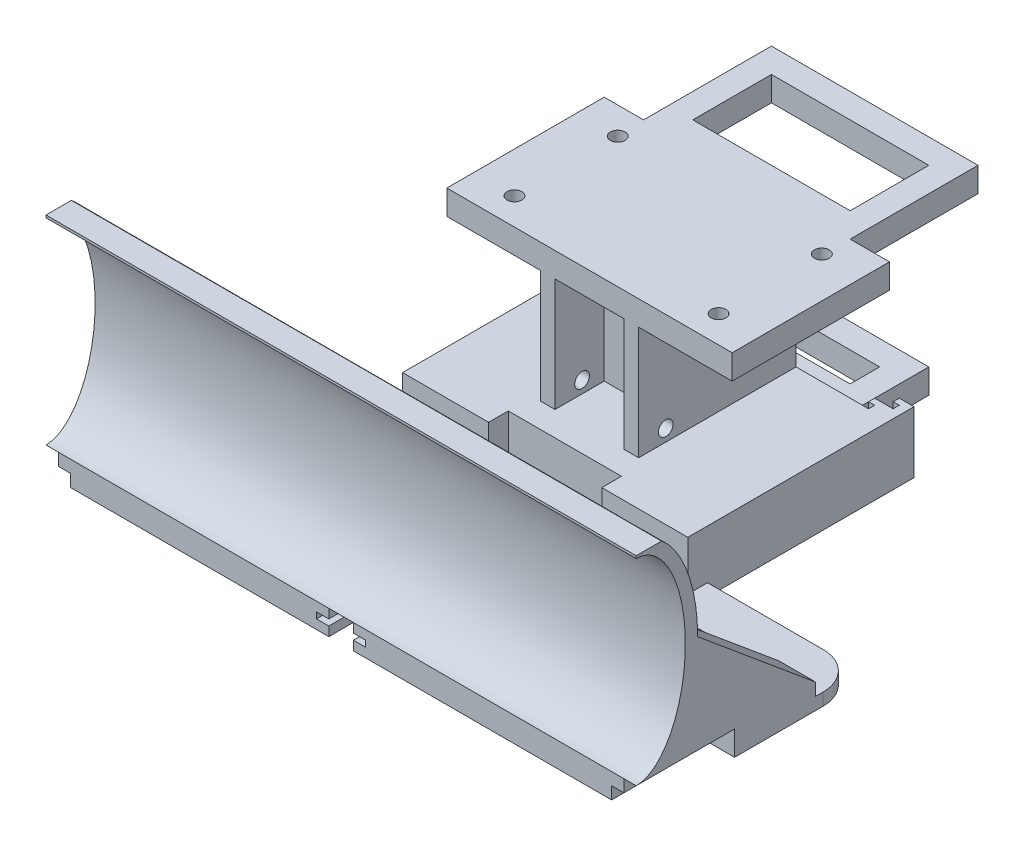
SolidWorks part; units mm, degrees
ref_plane "Alzado" through (0, 0, 0) normal (0, 0, 1) x (1, 0, 0)
ref_plane "Planta" through (0, 0, 0) normal (0, 1, 0) x (1, 0, 0)
ref_plane "Vista lateral" through (0, 0, 0) normal (1, 0, 0) x (0, 0, -1)
sketch "Base-Croquis" plane through (0, 0, 0) normal (0, 1, 0) x (1, 0, 0)
  line L1 (60, -60) -> (-60, -60)
  line L2 (60, -60) -> (60, 60)
  line L3 (60, 60) -> (-60, 60)
  line L4 (-60, -60) -> (-60, 60)
  line L5 (60, -60) -> (-60, 60) construction
  line L6 (60, 60) -> (-60, -60) construction
  point P0 (0, 0)
  dimension "D1" = 120
  dimension "D2" = 120
extrude "Base-Saliente" add sketch "Base-Croquis" along normal blind 5
sketch "Encaje-Ruedas-Croquis" plane through (0, 5, 0) normal (0, 1, 0) x (1, 0, 0)
  line L6 (60, 60) -> (29, 60)
  line L7 (60, 60) -> (60, 3)
  line L8 (60, 3) -> (29, 3)
  line L9 (29, 60) -> (29, 3)
  line L10 (0, -55) -> (0, 55) construction
  line L11 (-60, 3) -> (-29, 3)
  line L12 (-29, 60) -> (-29, 3)
  line L13 (-60, 60) -> (-29, 60)
  line L14 (-60, 60) -> (-60, 3)
  line L15 (60, 60) -> (60, 65) construction
  line L16 (60, 65) -> (-60, 65) construction
  line L17 (-60, 65) -> (-60, 60) construction
  line L18 (-31, 65) -> (-31, 60) construction
  line L19 (31, 65) -> (31, 60) construction
  dimension "D1" = 31
  dimension "D2" = 57
  dimension "D3" = 5
  dimension "D4" = 29
  dimension "D5" = 29
extrude "Encaje-Ruedas-Cortar" cut sketch "Encaje-Ruedas-Croquis" against normal blind 5
sketch "Caja-Placas-Croquis-1" plane through (0, 5, 0) normal (0, 1, 0) x (1, 0, 0)
  line L0 (29, 40) -> (-29, 40) construction
  line L1 (29, 60) -> (29, 3) construction
  line L2 (-29, 3) -> (-29, 60) construction
  line L3 (29, 60) -> (-29, 60) construction
  line L4 (-29, 8) -> (29, 8) construction
  line L5 (0, 8) -> (0, 40) construction
  line L7 (21, 8) -> (-21, 8)
  line L8 (21, 8) -> (21, 40)
  line L9 (21, 40) -> (-21, 40)
  line L10 (-21, 8) -> (-21, 40)
  line L11 (21, 8) -> (-21, 40) construction
  line L12 (21, 40) -> (-21, 8) construction
  line L13 (-29, 45) -> (29, 45)
  line L14 (-29, 45) -> (-29, 3)
  line L15 (-29, 3) -> (29, 3)
  line L16 (29, 45) -> (29, 3)
  point P12 (0, 24)
  dimension "D1" = 20
  dimension "D2" = 32
  dimension "D3" = 42
  dimension "D4" = 42
  dimension "D5" = 5
extrude "Caja-Placas-Saliente-1" add sketch "Caja-Placas-Croquis-1" along normal blind 5
sketch "Caja-Placas-Croquis-2" plane through (0, 5, 0) normal (0, 1, 0) x (1, 0, 0)
  line L0 (0, 3) -> (0, 45) construction
  line L1 (-29, 3) -> (29, 3) construction
  line L2 (29, 45) -> (-29, 45) construction
  line L4 (21, 8) -> (-21, 8)
  line L5 (21, 8) -> (21, 40)
  line L6 (21, 40) -> (-21, 40)
  line L7 (-21, 8) -> (-21, 40)
  line L8 (21, 8) -> (-21, 40) construction
  line L9 (21, 40) -> (-21, 8) construction
  point P6 (0, 24)
extrude "Caja-Placas-Cortar-2" cut sketch "Caja-Placas-Croquis-2" against normal blind 2.5
sketch "Caja-Placas-Croquis-3" plane through (0, 10, 0) normal (0, 1, 0) x (1, 0, 0)
  line L1 (-29, 45) -> (29, 45)
  line L2 (-29, 45) -> (-29, 3)
  line L3 (-29, 3) -> (29, 3)
  line L4 (29, 45) -> (29, 3)
extrude "Caja-Placas-Saliente-3" add sketch "Caja-Placas-Croquis-3" along normal blind 2.5
sketch "Caja-Placas-Croquis-4" plane through (0, 12.5, 0) normal (0, 1, 0) x (1, 0, 0)
  line L0 (-29, 40) -> (-29, 42.5) construction
  line L1 (-29, 42.5) -> (29, 42.5) construction
  line L2 (29, 45) -> (29, 3) construction
  line L3 (-29, 42.5) -> (-29, 45) construction
  line L4 (-29, 45) -> (29, 45) construction
  line L5 (29, 40) -> (-29, 40) construction
  line L6 (-29, 43.75) -> (29, 43.75) construction
  line L7 (-29, 41.25) -> (29, 41.25) construction
  line L8 (23.5, 42.5) -> (26, 42.5)
  line L9 (-23.5, 40) -> (23.5, 40)
  line L10 (-23.5, 41.25) -> (-23.5, 42.5)
  line L12 (23.5, 41.25) -> (23.5, 42.5)
  line L13 (-26, 45) -> (26, 45)
  line L14 (-26, 45) -> (-26, 43.75)
  line L15 (-26, 42.5) -> (-23.5, 42.5)
  line L16 (26, 45) -> (26, 43.75)
  line L17 (26, 43.75) -> (27.25, 43.75)
  line L19 (26, 42.5) -> (27.25, 42.5)
  line L20 (27.25, 43.75) -> (27.25, 42.5)
  line L21 (23.5, 41.25) -> (24.75, 41.25)
  line L23 (23.5, 40) -> (24.75, 40)
  line L24 (24.75, 41.25) -> (24.75, 40)
  line L25 (-23.5, 40) -> (-24.75, 40)
  line L27 (-23.5, 41.25) -> (-24.75, 41.25)
  line L28 (-24.75, 40) -> (-24.75, 41.25)
  line L29 (-26, 42.5) -> (-27.25, 42.5)
  line L31 (-26, 43.75) -> (-27.25, 43.75)
  line L32 (-27.25, 42.5) -> (-27.25, 43.75)
  dimension "D1" = 47
  dimension "D2" = 5.5
  dimension "D3" = 52
  dimension "D4" = 3
  dimension "D5" = 1.25
  dimension "D6" = 1.25
  dimension "D7" = 1.25
  dimension "D8" = 1.25
extrude "Caja-Placas-Cortar-4" cut sketch "Caja-Placas-Croquis-4" against normal blind 7.5
sketch "Caja-Placas-Croquis-5" plane through (0, 0, 0) normal (0, -1, 0) x (-1, 0, 0)
  line L0 (0, 8) -> (0, 40) construction
  line L1 (15.5, 34.5) -> (-15.5, 34.5)
  line L2 (15.5, 34.5) -> (15.5, 13.5)
  line L3 (15.5, 13.5) -> (-15.5, 13.5)
  line L4 (-15.5, 34.5) -> (-15.5, 13.5)
  line L5 (15.5, 34.5) -> (-15.5, 13.5) construction
  line L6 (15.5, 13.5) -> (-15.5, 34.5) construction
  point P0 (0, 24)
  dimension "D1" = 21
  dimension "D2" = 31
extrude "Caja-Placas-Cortar-5" cut sketch "Caja-Placas-Croquis-5" against normal blind 2.5
sketch "Caja-Motores-Croquis-1" plane through (0, 12.5, 0) normal (0, 1, 0) x (1, 0, 0)
  line L0 (21, 8) -> (-21, 40) construction
  line L1 (-10, 8) -> (10, 8)
  line L2 (-10, 8) -> (-10, 40)
  line L3 (-10, 40) -> (10, 40)
  line L4 (10, 8) -> (10, 40)
  line L5 (-10, 8) -> (10, 40) construction
  line L6 (-10, 40) -> (10, 8) construction
  line L7 (21, 40) -> (-21, 40) construction
  point P0 (0, 24)
  dimension "D1" = 20
extrude "Caja-Motores-Saliente-1" add sketch "Caja-Motores-Croquis-1" along normal blind 23
sketch "Agujero-Tornillo-M3-Croquis" plane through (10, 0, 0) normal (1, 0, 0) x (0, 0, -1)
  line L0 (13.5, 35.5) -> (13.5, 12.5) construction
  line L1 (8, 35.5) -> (40, 35.5) construction
  line L2 (3, 12.5) -> (45, 12.5) construction
  line L3 (40, 35.5) -> (40, 12.5) construction
  circle A0 centre (33.5, 23.7) radius 5
  circle A1 centre (13.5, 32.45) radius 1.5
  circle A2 centre (13.5, 14.95) radius 1.5
  dimension "D1" = 10
  dimension "D2" = 3
  dimension "D3" = 3.05
  dimension "D4" = 2.45
  dimension "D5" = 11.8
  dimension "D6" = 6.5
extrude "Agujero-Tornillo-M3-Cortar" cut sketch "Agujero-Tornillo-M3-Croquis" against normal blind 20
sketch "Caja-Motores-Croquis-2" plane through (0, 35.5, 0) normal (0, 1, 0) x (1, 0, 0)
  line L1 (-29, 8) -> (29, 8)
  line L2 (-29, 8) -> (-29, 40)
  line L3 (-29, 40) -> (29, 40)
  line L4 (29, 8) -> (29, 40)
  line L5 (-29, 8) -> (29, 40) construction
  line L6 (-29, 40) -> (29, 8) construction
  point P0 (0, 24)
extrude "Caja-Motores-Saliente-2" add sketch "Caja-Motores-Croquis-2" along normal blind 5
sketch "Ajugero-Tuercas-M3-Croquis" plane through (0, 0, -8) normal (0, 0, 1) x (1, 0, 0)
  line L0 (-29, 35.5) -> (29, 35.5) construction
  line L1 (-29, 12.5) -> (29, 12.5) construction
  line L2 (-7, 35.5) -> (7, 35.5)
  line L3 (-7, 35.5) -> (-7, 12.5)
  line L4 (-7, 12.5) -> (7, 12.5)
  line L5 (7, 35.5) -> (7, 12.5)
  line L6 (-10, 35.5) -> (-10, 12.5) construction
  line L7 (10, 35.5) -> (10, 12.5) construction
  dimension "D1" = 3
  dimension "D2" = 3
extrude "Ajugero-Tuercas-M3-Cortar" cut sketch "Ajugero-Tuercas-M3-Croquis" against normal blind 10
sketch "Agujer-PCB-Tarugo-Croquis" plane through (0, 40.5, 0) normal (0, 1, 0) x (1, 0, 0)
  line L0 (0, 8) -> (0, 40) construction
  line L1 (-21, 24) -> (21, 24) construction
  line L2 (-21, 8) -> (-21, 40) construction
  line L3 (21, 8) -> (21, 40) construction
  line L4 (0, 40) -> (0, 8) construction
  line L5 (21, 8) -> (-21, 8) construction
  circle A0 centre (-20.75, 34.5) radius 1.5
  circle A1 centre (20.75, 34.5) radius 1.5
  circle A2 centre (-20.75, 13.5) radius 1.5
  circle A3 centre (20.75, 13.5) radius 1.5
  dimension "D3" = 3
  dimension "D1" = 20.75
  dimension "D2" = 10.5
extrude "Agujer-PCB-Tarugo-Cortar" cut sketch "Agujer-PCB-Tarugo-Croquis" against normal blind 3
sketch "Croquis13" plane through (0, 40.5, 0) normal (0, 1, 0) x (1, 0, 0)
  line L0 (21, 40) -> (-21, 40) construction
  line L1 (-21, 40) -> (21, 40)
  line L2 (-21, 40) -> (-21, 66)
  line L3 (-21, 66) -> (21, 66)
  line L4 (21, 40) -> (21, 66)
  line L5 (0, 40) -> (0, 66) construction
  line L7 (-16, 45) -> (16, 45)
  line L8 (-16, 45) -> (-16, 61)
  line L9 (-16, 61) -> (16, 61)
  line L10 (16, 45) -> (16, 61)
  line L11 (-16, 45) -> (16, 61) construction
  line L12 (-16, 61) -> (16, 45) construction
  point P6 (0, 40)
  point P10 (0, 53)
  dimension "D1" = 26
  dimension "D2" = 42
  dimension "D3" = 16
  dimension "D4" = 32
extrude "Caja-Bateria-Saliente" add sketch "Croquis13" against normal blind 5
sketch "Caja-Placas-Laterales-Croquis-1" plane through (0, 5, 0) normal (0, 1, 0) x (1, 0, 0)
  line L0 (-60, -1) -> (60, -1) construction
  line L1 (-60, 3) -> (-60, -60) construction
  line L2 (60, -60) -> (60, 3) construction
  line L3 (-60, 3) -> (-29, 3) construction
  line L4 (0, 0) -> (0, -60) construction
  line L5 (-52.5, -1) -> (-11.5, -1)
  line L6 (-52.5, -1) -> (-52.5, -32)
  line L7 (-52.5, -32) -> (-11.5, -32)
  line L8 (-11.5, -1) -> (-11.5, -32)
  line L9 (-60, -60) -> (60, -60) construction
  line L10 (52.5, -32) -> (11.5, -32)
  line L11 (11.5, -1) -> (11.5, -32)
  line L12 (52.5, -1) -> (11.5, -1)
  line L13 (52.5, -1) -> (52.5, -32)
  dimension "D1" = 4
  dimension "D2" = 41
  dimension "D3" = 31
  dimension "D4" = 7.5
extrude "Caja-Placas-Laterales-Cortar-1" cut sketch "Caja-Placas-Laterales-Croquis-1" against normal blind 2.5
sketch "Caja-Placas-Laterales-Croquis-2" plane through (0, 5, 0) normal (0, 1, 0) x (1, 0, 0)
  line L0 (60, -60) -> (60, 3) construction
  line L1 (52.5, -1) -> (60, -1)
  line L2 (52.5, -1) -> (52.5, -6)
  line L3 (52.5, -6) -> (60, -6)
  line L4 (60, -1) -> (60, -6)
  line L5 (0, 0) -> (0, -60) construction
  line L6 (-60, -60) -> (60, -60) construction
  line L7 (-52.5, -6) -> (-60, -6)
  line L8 (-60, -1) -> (-60, -6)
  line L9 (-52.5, -1) -> (-60, -1)
  line L10 (-52.5, -1) -> (-52.5, -6)
  dimension "D1" = 5
extrude "Caja-Placas-Laterales-Cortar-2" cut sketch "Caja-Placas-Laterales-Croquis-2" against normal blind 2.5
sketch "Caja-Placas-Laterales-Croquis-3" plane through (0, 2.5, 0) normal (0, 1, 0) x (1, 0, 0)
  line L0 (11.5, -16.5) -> (52.5, -16.5) construction
  line L1 (11.5, -1) -> (11.5, -32) construction
  line L2 (52.5, -32) -> (52.5, -6) construction
  line L3 (0, 0) -> (0, -60) construction
  line L4 (16.5, -27) -> (47.5, -27)
  line L5 (16.5, -27) -> (16.5, -6)
  line L6 (16.5, -6) -> (47.5, -6)
  line L7 (47.5, -27) -> (47.5, -6)
  line L8 (16.5, -27) -> (47.5, -6) construction
  line L9 (16.5, -6) -> (47.5, -27) construction
  line L10 (-16.5, -6) -> (-47.5, -6)
  line L11 (-47.5, -27) -> (-47.5, -6)
  line L12 (-16.5, -27) -> (-47.5, -27)
  line L13 (-16.5, -27) -> (-16.5, -6)
  point P6 (32, -16.5)
  dimension "D1" = 21
  dimension "D2" = 31
extrude "Caja-Placas-Laterales-Cortar-3" cut sketch "Caja-Placas-Laterales-Croquis-3" against normal blind 2.5
sketch "Parachoques-Croquis-1" plane through (60, 0, 0) normal (1, 0, 0) x (0, 0, -1)
  line L0 (-32, 5) -> (-32, 0) construction
  line L1 (-60, 5) -> (-6, 5) construction
  line L2 (-60, 0) -> (3, 0) construction
  line L3 (3, 0) -> (3, 5) construction
  line L4 (-42.5, 0) -> (-42.5, 5) construction
  line L5 (-42.5, -18.0112) -> (-42.5, 57.6163) construction
  line L6 (-42.5, 45) -> (-30, 45) construction
  line L7 (-42.5, 5) -> (-32, 5) construction
  line L8 (-42.5, 5) -> (-36.7735, 5)
  line L16 (-42.5, 45) -> (-42.5, 45.5)
  line L17 (-42.5, 45.5) -> (-37.348, 45.5)
  ellipse E0 centre (-42.5, 25) end of major axis (-42.5, 45) minor radius 10 (-42.5, 5) -> (-42.5, 45) ccw
  ellipse E1 centre (-42.5, 25) end of major axis (-42.5, 2.5) minor radius 12.5 (-36.7735, 5) -> (-37.348, 45.5) ccw
  dimension "D1" = 35
  dimension "D2" = 10.5
  dimension "D3" = 20
  dimension "D4" = 10
  dimension "D5" = 12.5
  dimension "D6" = 22.5
  dimension "D7" = 0.5
extrude "Parachoques-Saliente-1" add sketch "Parachoques-Croquis-1" against normal blind 120
sketch "Parachoques-Croquis-2" plane through (60, 0, 0) normal (1, 0, 0) x (0, 0, -1)
  line L0 (-30, 25) -> (-6, 5)
  line L1 (-6, 5) -> (-36.7735, 5)
  line L2 (-30, 25) -> (-42.5, 25) construction
  line L3 (-42.5, 25) -> (-42.5, 2.5) construction
  ellipse E0 centre (-42.5, 25) end of major axis (-42.5, 2.5) minor radius 12.5 (-36.7735, 5) -> (-37.348, 45.5) ccw construction
  ellipse E1 centre (-42.5, 25) end of major axis (-42.5, 2.5) minor radius 12.5 (-30, 25) -> (-36.7735, 5) cw
  dimension "D1" = 22.5
extrude "Parachoques-Saliente-2" add sketch "Parachoques-Croquis-2" against normal blind 7.5
sketch "Parachoques-Croquis-3" plane through (-60, 0, 0) normal (-1, 0, 0) x (0, 0, 1)
  line L0 (6, 5) -> (30, 25)
  line L1 (6, 5) -> (36.7735, 5)
  line L2 (30, 25) -> (42.5, 25) construction
  line L3 (42.5, 25) -> (42.5, 2.5) construction
  ellipse E0 centre (42.5, 25) end of major axis (42.5, 2.5) minor radius 12.5 (30, 25) -> (36.7735, 5) ccw
  dimension "D1" = 22.5
extrude "Parachoques-Saliente-3" add sketch "Parachoques-Croquis-3" against normal blind 7.5
sketch "Parachoques-Croquis-4" plane through (0, 0, 0) normal (1, 0, 0) x (0, 0, -1)
  line L0 (-30, 25) -> (-42.5, 25) construction
  line L1 (-6, 5) -> (-30, 25) construction
  line L2 (-42.5, 25) -> (-42.5, 2.5) construction
  line L3 (-6, 5) -> (-30, 25)
  line L4 (-6, 5) -> (-36.7735, 5)
  ellipse E0 centre (-42.5, 25) end of major axis (-42.5, 2.5) minor radius 12.5 (-30, 25) -> (-37.348, 45.5) ccw construction
  ellipse E1 centre (-42.5, 25) end of major axis (-42.5, 2.5) minor radius 12.5 (-30, 25) -> (-36.7735, 5) cw
  dimension "D1" = 22.5
extrude "Parachoques-Saliente-4" add sketch "Parachoques-Croquis-4" against normal blind 5 from vertex starting at point (11.5, 5, 32)
sketch "Parachoques-Croquis-6" plane through (0, 0, 0) normal (1, 0, 0) x (0, 0, -1)
  line L0 (-30, 25) -> (-42.5, 25) construction
  line L2 (-42.5, 25) -> (-42.5, 2.5) construction
  line L3 (-6, 5) -> (-30, 25)
  line L4 (-6, 5) -> (-36.7735, 5)
  ellipse E1 centre (-42.5, 25) end of major axis (-42.5, 2.5) minor radius 12.5 (-30, 25) -> (-36.7735, 5) cw
  dimension "D1" = 22.5
extrude "Parachoques-Saliente-5" add sketch "Parachoques-Croquis-6" along normal blind 3.75 and the other way blind 3.75
extrude "Parachoques-Saliente-6" add sketch "Croquis9<2>" along normal blind 5 from vertex starting at point (-11.5, 5, 32)
sketch "Croquis9<2>" plane through (0, 0, 0) normal (1, 0, 0) x (0, 0, -1) same geometry as "Parachoques-Croquis-6"
sketch "Croquis12" plane through (0, 5, 0) normal (0, 1, 0) x (1, 0, 0)
  line L5 (-60, -42.5) -> (60, -42.5)
  line L6 (-60, -42.5) -> (-60, -60)
  line L7 (-60, -60) -> (60, -60)
  line L8 (60, -42.5) -> (60, -60)
extrude "Encaje-Cuchilla-Cortar-1" cut sketch "Croquis12" against normal blind 5
sketch "Encaje-Cuchilla-Lateral-Croquis-1" plane through (0, 0, 0) normal (0, -1, 0) x (1, 0, 0)
  line L0 (0, 0) -> (0, 42.5) construction
  line L1 (60, 42.5) -> (55, 42.5)
  line L2 (60, 42.5) -> (60, 22.5)
  line L3 (60, 22.5) -> (55, 22.5)
  line L4 (55, 42.5) -> (55, 22.5)
  line L5 (60, 42.5) -> (-60, 42.5) construction
  line L6 (-60, 22.5) -> (-55, 22.5)
  line L7 (-55, 42.5) -> (-55, 22.5)
  line L8 (-60, 42.5) -> (-55, 42.5)
  line L9 (-60, 42.5) -> (-60, 22.5)
  dimension "D1" = 5
  dimension "D2" = 20
extrude "Encaje-Cuchilla-Lateral-Cortar-1" cut sketch "Encaje-Cuchilla-Lateral-Croquis-1" against normal blind 2.5
sketch "Encaje-Cuchilla-Lateral-Croquis-2" plane through (0, 2.5, 0) normal (0, -1, 0) x (1, 0, 0)
  line L0 (55, 22.5) -> (60, 22.5) construction
  line L1 (60, 42.5) -> (57.5, 42.5)
  line L2 (60, 42.5) -> (60, 22.5)
  line L3 (60, 22.5) -> (57.5, 22.5)
  line L4 (57.5, 42.5) -> (57.5, 22.5)
  line L5 (0, 42.5) -> (0, 0) construction
  line L6 (55, 42.5) -> (-55, 42.5) construction
  line L7 (-60, 22.5) -> (-57.5, 22.5)
  line L8 (-57.5, 42.5) -> (-57.5, 22.5)
  line L9 (-60, 42.5) -> (-57.5, 42.5)
  line L10 (-60, 42.5) -> (-60, 22.5)
extrude "Encaje-Cuchilla-Lateral-Cortar-2" cut sketch "Encaje-Cuchilla-Lateral-Croquis-2" against normal blind 2.5
sketch "Encaje-Cuchilla-Lateral-Croquis-3" plane through (57.5, 0, 0) normal (1, 0, 0) x (0, 0, -1)
  line L1 (-22.5, 5) -> (-25, 5)
  line L2 (-22.5, 5) -> (-22.5, 3.75)
  line L3 (-22.5, 3.75) -> (-25, 3.75)
  line L4 (-25, 5) -> (-25, 3.75)
  dimension "D1" = 2.5
  dimension "D2" = 1.25
extrude "Encaje-Cuchilla-Lateral-Cortar-3" cut sketch "Encaje-Cuchilla-Lateral-Croquis-3" against normal blind 1.25
sketch "Encaje-Cuchilla-Lateral-Croquis-4" plane through (55, 0, 0) normal (1, 0, 0) x (0, 0, -1)
  line L0 (-22.5, 5) -> (-22.5, 0) construction
  line L1 (-22.5, 2.5) -> (-25, 2.5)
  line L2 (-22.5, 2.5) -> (-22.5, 1.25)
  line L3 (-22.5, 1.25) -> (-25, 1.25)
  line L4 (-25, 2.5) -> (-25, 1.25)
  dimension "D1" = 2.5
  dimension "D2" = 1.25
extrude "Encaje-Cuchilla-Lateral-Cortar-4" cut sketch "Encaje-Cuchilla-Lateral-Croquis-4" against normal blind 1.25
sketch "Encaje-Cuchilla-Lateral-Croquis-5" plane through (-57.5, 0, 0) normal (-1, 0, 0) x (0, 0, 1)
  line L1 (22.5, 5) -> (25, 5)
  line L2 (22.5, 5) -> (22.5, 3.75)
  line L3 (22.5, 3.75) -> (25, 3.75)
  line L4 (25, 5) -> (25, 3.75)
  dimension "D1" = 1.25
  dimension "D2" = 2.5
extrude "Encaje-Cuchilla-Lateral-Cortar-5" cut sketch "Encaje-Cuchilla-Lateral-Croquis-5" against normal blind 1.25
sketch "Encaje-Cuchilla-Lateral-Croquis-6" plane through (-55, 0, 0) normal (-1, 0, 0) x (0, 0, 1)
  line L0 (22.5, 5) -> (22.5, 0) construction
  line L1 (22.5, 2.5) -> (25, 2.5)
  line L2 (22.5, 2.5) -> (22.5, 1.25)
  line L3 (22.5, 1.25) -> (25, 1.25)
  line L4 (25, 2.5) -> (25, 1.25)
  dimension "D1" = 1.25
  dimension "D2" = 2.5
extrude "Encaje-Cuchilla-Lateral-Cortar-6" cut sketch "Encaje-Cuchilla-Lateral-Croquis-6" against normal blind 1.25
sketch "Encaje-Cuchilla-Central-Croquis" plane through (0, 0, 42.5) normal (0, 0, 1) x (1, 0, 0)
  line L0 (0, 0) -> (0, 5) construction
  line L1 (-29, 5) -> (29, 5) construction
  line L2 (-2.5, 0) -> (2.5, 0)
  line L3 (-2.5, 0) -> (-2.5, 1.875)
  line L4 (-2.5, 5) -> (2.5, 5)
  line L5 (2.5, 0) -> (2.5, 1.875)
  line L6 (-2.5, 0) -> (2.5, 5) construction
  line L7 (-2.5, 5) -> (2.5, 0) construction
  line L8 (-2.5, 3.125) -> (-2.5, 5)
  line L9 (-5, 1.875) -> (-2.5, 1.875)
  line L10 (-5, 1.875) -> (-5, 3.125)
  line L11 (-5, 3.125) -> (-2.5, 3.125)
  line L12 (5, 1.875) -> (5, 3.125)
  line L13 (-5, 1.875) -> (5, 3.125) construction
  line L14 (-5, 3.125) -> (5, 1.875) construction
  line L16 (2.5, 1.875) -> (5, 1.875)
  line L17 (2.5, 3.125) -> (2.5, 5)
  line L18 (2.5, 3.125) -> (5, 3.125)
  point P4 (0, 2.5)
  point P11 (0, 2.5)
  dimension "D1" = 5
  dimension "D2" = 10
  dimension "D3" = 1.25
extrude "Encaje-Cuchilla-Central-Cortar" cut sketch "Encaje-Cuchilla-Central-Croquis" against normal blind 20
sketch "Croquis14" plane through (0, 5, 0) normal (0, 1, 0) x (1, 0, 0)
  line L0 (-16, 61) -> (-16, 45) construction
  line L1 (-29, 45) -> (-16, 45)
  line L2 (-29, 45) -> (-29, 60)
  line L3 (-29, 60) -> (-16, 60)
  line L4 (-16, 45) -> (-16, 60)
  line L5 (29, 60) -> (-29, 60) construction
  line L6 (0, 45) -> (0, 61) construction
  line L7 (-29, 45) -> (29, 45) construction
  line L8 (16, 61) -> (-16, 61) construction
  line L9 (29, 60) -> (16, 60)
  line L10 (16, 45) -> (16, 60)
  line L11 (29, 45) -> (16, 45)
  line L12 (29, 45) -> (29, 60)
extrude "Detalles-Ajustes-1" cut sketch "Croquis14" against normal blind 5
sketch "Croquis15" plane through (0, 5, 0) normal (0, 1, 0) x (1, 0, 0)
  line L1 (-16, 60) -> (16, 60)
  line L2 (-16, 60) -> (-16, 61)
  line L3 (-16, 61) -> (16, 61)
  line L4 (16, 60) -> (16, 61)
extrude "Detalles-Ajustes-2" add sketch "Croquis15" against normal blind 5
sketch "Croquis16" plane through (0, 5, 0) normal (0, 1, 0) x (1, 0, 0)
  line L0 (-16, 53) -> (16, 53) construction
  line L1 (-16, 61) -> (-16, 45) construction
  line L2 (16, 45) -> (16, 61) construction
  line L4 (-11, 50) -> (11, 50)
  line L5 (-11, 50) -> (-11, 56)
  line L6 (-11, 56) -> (11, 56)
  line L7 (11, 50) -> (11, 56)
  line L8 (-11, 50) -> (11, 56) construction
  line L9 (-11, 56) -> (11, 50) construction
  point P6 (0, 53)
  dimension "D1" = 6
  dimension "D2" = 22
extrude "Detalles-Ajustes-3" cut sketch "Croquis16" against normal blind 5
sketch "Croquis17" plane through (0, 5, 0) normal (0, 1, 0) x (1, 0, 0)
  line L1 (-60, 3) -> (-29, 3) construction
  line L2 (0, -6) -> (0, 3) construction
  line L3 (-11.5, -1) -> (-29, -1)
  line L4 (-11.5, -1) -> (-11.5, 3)
  line L5 (-11.5, 3) -> (-29, 3)
  line L6 (-29, -1) -> (-29, 3)
  line L7 (-3.75, -6) -> (3.75, -6) construction
  line L8 (11.5, 3) -> (29, 3)
  line L9 (29, -1) -> (29, 3)
  line L10 (11.5, -1) -> (29, -1)
  line L11 (11.5, -1) -> (11.5, 3)
  point P0 (-29, 3)
extrude "Detalles-Ajustes-4" add sketch "Croquis17" along normal blind 7.5
sketch "Croquis18" plane through (0, 5, 0) normal (0, 1, 0) x (1, 0, 0)
  line L0 (-29, 45) -> (-29, -1) construction
  line L1 (-60, 3) -> (-29, 3)
  line L2 (-60, 3) -> (-60, -1)
  line L3 (-60, -1) -> (-29, -1)
  line L4 (-29, 3) -> (-29, -1)
  line L5 (-29, -1) -> (-60, -1) construction
  line L6 (0, -6) -> (0, 3) construction
  line L7 (-3.75, -6) -> (3.75, -6) construction
  line L8 (-29, 3) -> (29, 3) construction
  line L9 (60, -1) -> (29, -1)
  line L10 (29, 3) -> (29, -1)
  line L11 (60, 3) -> (29, 3)
  line L12 (60, 3) -> (60, -1)
extrude "Detalles-Ajustes-5" cut sketch "Croquis18" against normal blind 2.5
sketch "Croquis19" plane through (0, 2.5, 0) normal (0, 1, 0) x (1, 0, 0)
  line L0 (60, -4.5) -> (52.5, -4.5) construction
  line L1 (60, -6) -> (60, 3) construction
  line L2 (60, 3) -> (29, 3) construction
  line L3 (52.5, 3) -> (60, 3)
  line L4 (60, 3) -> (60, -4.5)
  line L5 (0, -6) -> (0, 3) construction
  line L6 (-3.75, -6) -> (3.75, -6) construction
  line L7 (-29, 3) -> (29, 3) construction
  line L8 (-60, 3) -> (-60, -4.5)
  line L9 (-52.5, 3) -> (-60, 3)
  arc A0 (60, -4.5) -> (52.5, 3) centre (52.5, -4.5) ccw
  arc A1 (-60, -4.5) -> (-52.5, 3) centre (-52.5, -4.5) cw
  dimension "D1" = 7.5
  dimension "D2" = 7.5
extrude "Detalles-Ajustes-6" cut sketch "Croquis19" against normal blind 2.5
